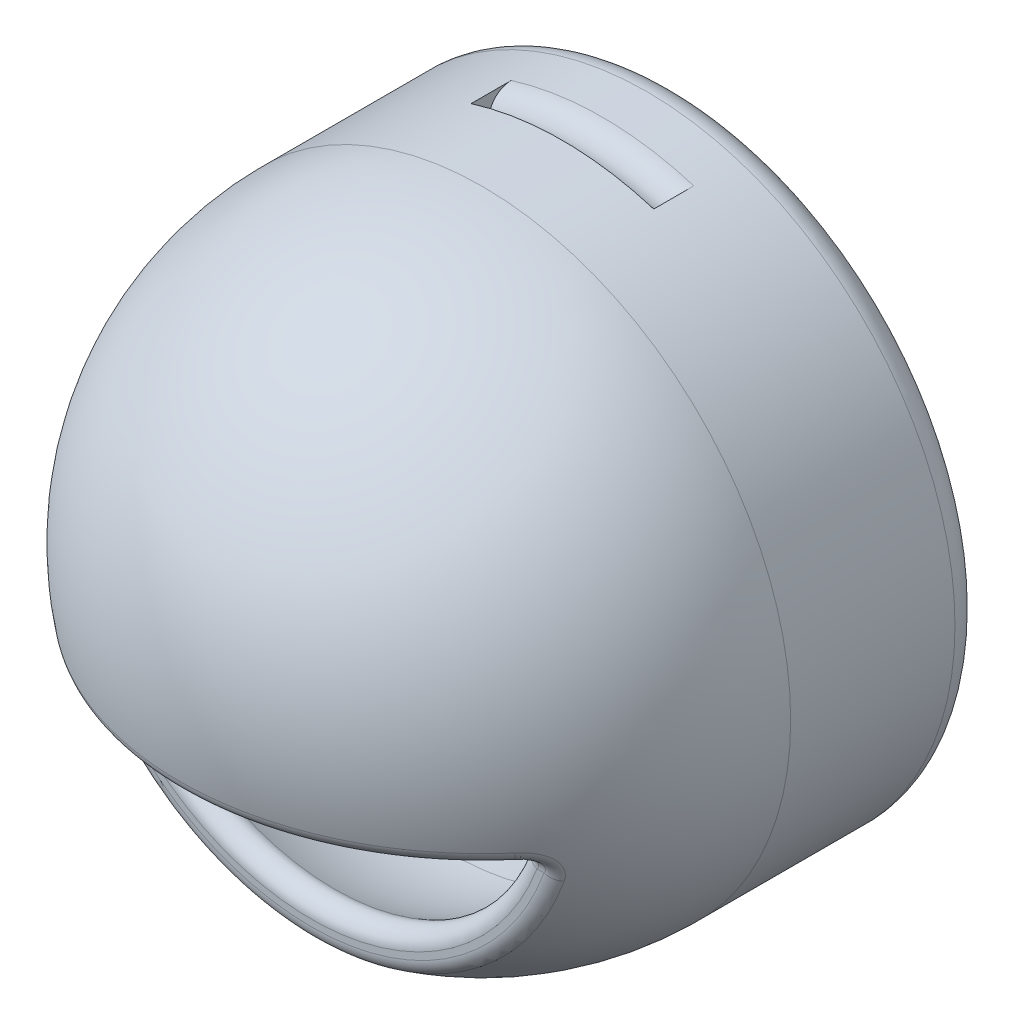
SolidWorks part; units mm, degrees
ref_plane "Front Plane" through (0, 0, 0) normal (0, 0, 1) x (1, 0, 0)
ref_plane "Top Plane" through (0, 0, 0) normal (0, 1, 0) x (1, 0, 0)
ref_plane "Right Plane" through (0, 0, 0) normal (1, 0, 0) x (0, 0, -1)
sketch "Sketch1" plane through (0, 0, 0) normal (0, 0, 1) x (1, 0, 0)
  circle A0 centre (0, 0) radius 13.5
extrude "Boss-Extrude1" add sketch "Sketch1" along normal blind 22 contours A0
sketch "Sketch2" plane through (0, 0, 0) normal (0, 0, -1) x (-1, 0, 0)
  circle A0 centre (0, 0) radius 11.2
extrude "Cut-Extrude1" cut sketch "Sketch2" against normal blind 21 contours A0
fillet "Fillet1" radius 13.5 1 edges at (13.5, 0, 22)
fillet "Fillet2" radius 11.2 1 edges at (-11.2, 0, 21)
fillet "Fillet3" radius 1 1 edges at (-11.2, 0, 0)
sketch "Sketch5" plane through (0, 0, 0) normal (0, 0, -1) x (-1, 0, 0)
  line L3 (5.5, 11.25) -> (-5.5, 11.25)
  line L4 (5.5, 11.25) -> (5.5, 7.5)
  line L5 (5.5, 7.5) -> (-5.5, 7.5)
  line L6 (-5.5, 11.25) -> (-5.5, 7.5)
  point P0 (0, 0)
extrude "Cut-Extrude5" cut sketch "Sketch5" against normal blind 12
sketch "Sketch6" plane through (0, 11.25, 0) normal (0, -1, 0) x (1, 0, 0)
  line L0 (0, 5) -> (4, 5)
  line L1 (4, 5) -> (4, 4.2428)
  line L2 (4, 4.2428) -> (-4, 4.2428)
  line L3 (-4, 4.2428) -> (-4, 5)
  line L4 (-4, 5) -> (0, 5)
extrude "Cut-Extrude7" cut sketch "Sketch6" against normal mid plane 52
fillet "Fillet6" radius 1 1 edges at (0, 11.25, 4.2428)
fillet "Fillet7" radius 1 1 edges at (0, 13.5, 4.2428)
fillet "Fillet8" radius 1 1 edges at (0, -11.2, 4.2428)
fillet "Fillet9" radius 1 1 edges at (0, -13.5, 4.2428)
fillet "Fillet10" radius 1.3 1 edges at (13.5, 0, 0)
sketch3d "3DSketch4"
  line L1 (13.7989, -3, 16) -> (13.7989, -3, 25.3954)
  line L2 (13.7989, -3, 16) -> (-14.0618, -3, 16)
  line L3 (-14.0618, -3, 16) -> (-14.0618, -3, 25.3954)
  line L4 (13.7989, -3, 25.3954) -> (-14.0618, -3, 25.3954)
  point P4 (0, 0, 0)
  point P5 (0, 0, 0)
  point P6 (0, 0, 0)
  point P7 (0, 0, 0)
  point P8 (0, 0, 0)
  point P9 (0, 0, 0)
  point P10 (0, 0, 0)
extrude "Cut-Extrude8" cut sketch "3DSketch4" along direction (0, 1, 0) on the side of the normal blind 10
fillet "Fillet12" radius 0.7 6 edges at (0, -11.225, 16) (0, -9.3274, 16) (0, -3, 21.6624) (0, -3, 20.5907)
